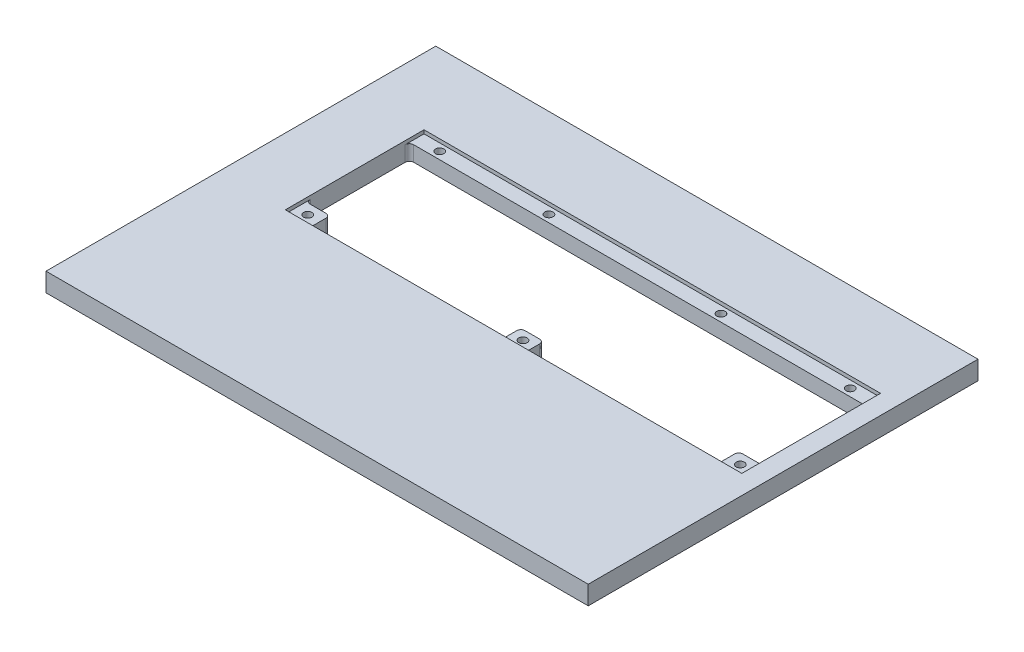
SolidWorks part; units mm, degrees
ref_plane "Front Plane" through (0, 0, 0) normal (0, 0, 1) x (1, 0, 0)
ref_plane "Top Plane" through (0, 0, 0) normal (0, 1, 0) x (1, 0, 0)
ref_plane "Right Plane" through (0, 0, 0) normal (1, 0, 0) x (0, 0, -1)
sketch "Sketch1" plane through (0, 0, 0) normal (0, 1, 0) x (1, 0, 0)
  line L1 (-15, 0) -> (245, 0)
  line L2 (-15, 0) -> (-15, 186.9)
  line L3 (-15, 186.9) -> (245, 186.9)
  line L4 (245, 0) -> (245, 186.9)
  point P5 (0, 0)
  point P6 (0, 0)
  point P7 (0, 0)
  point P8 (0, 0)
  point P9 (0, 0)
  dimension "D1" = 186.9
  dimension "D2" = 260
extrude "Boss-Extrude1" add sketch "Sketch1" along normal blind 9
sketch "Sketch2" plane through (0, 0, 0) normal (0, 1, 0) x (1, 0, 0)
  line L0 (245, 186.9) -> (-15, 186.9) construction
  line L1 (16.91, 149.35) -> (235.81, 149.35)
  line L2 (16.91, 149.35) -> (16.91, 82.85)
  line L3 (16.91, 82.85) -> (235.81, 82.85)
  line L4 (235.81, 149.35) -> (235.81, 82.85)
  dimension "D1" = 37.55
  dimension "D3" = 66.5
  dimension "D4" = 218.9
extrude "Cut-Extrude1" cut sketch "Sketch2" along normal blind 9
sketch "Sketch3" plane through (0, 9, 0) normal (0, 1, 0) x (1, 0, 0)
  line L0 (235.81, 149.35) -> (16.91, 149.35) construction
  line L1 (16.91, 149.35) -> (16.91, 82.85) construction
  line L2 (16.91, 82.85) -> (235.81, 82.85) construction
  circle A0 centre (27.91, 145.85) radius 2
  circle A1 centre (80.31, 145.85) radius 2
  circle A2 centre (162.81, 145.85) radius 2
  circle A3 centre (224.81, 145.85) radius 2
  circle A4 centre (22.66, 87.85) radius 2
  circle A5 centre (126.36, 87.35) radius 2
  circle A6 centre (230.06, 87.85) radius 2
  dimension "D3" = 4
  dimension "D4" = 3.5
  dimension "D6" = 3.5
  dimension "D8" = 3.5
  dimension "D10" = 5
  dimension "D12" = 4.5
  dimension "D14" = 5
  dimension "D1" = 3.5
  dimension "D2" = 11
  dimension "D5" = 52.4
  dimension "D7" = 82.5
  dimension "D9" = 62
  dimension "D11" = 5.75
  dimension "D13" = 103.7
  dimension "D15" = 103.7
sketch "Sketch4" plane through (0, 0, 0) normal (0, 1, 0) x (1, 0, 0)
  line L0 (235.81, 82.85) -> (235.81, 149.35) construction
  line L1 (16.91, 149.35) -> (235.81, 149.35)
  line L2 (16.91, 149.35) -> (16.91, 142.35)
  line L3 (16.91, 142.35) -> (235.81, 142.35)
  line L4 (235.81, 149.35) -> (235.81, 142.35)
  line L5 (16.91, 82.85) -> (235.81, 82.85) construction
  line L6 (235.81, 82.85) -> (224.31, 82.85)
  line L7 (235.81, 82.85) -> (235.81, 92.85)
  line L8 (235.81, 92.85) -> (224.31, 92.85)
  line L9 (224.31, 82.85) -> (224.31, 92.85)
  line L10 (120.86, 82.85) -> (131.86, 82.85)
  line L11 (120.86, 82.85) -> (120.86, 91.85)
  line L12 (120.86, 91.85) -> (131.86, 91.85)
  line L13 (131.86, 82.85) -> (131.86, 91.85)
  line L15 (16.91, 82.85) -> (28.41, 82.85)
  line L16 (16.91, 82.85) -> (16.91, 92.85)
  line L17 (16.91, 92.85) -> (28.41, 92.85)
  line L18 (28.41, 82.85) -> (28.41, 92.85)
  dimension "D1" = 7
  dimension "D2" = 5
  dimension "D3" = 5.75
  dimension "D4" = 4.5
  dimension "D5" = 5.5
  dimension "D6" = 5.5
  dimension "D7" = 5.75
  dimension "D8" = 5
extrude "Boss-Extrude2" add sketch "Sketch4" along normal blind 7.3
extrude "Cut-Extrude2" cut sketch "Sketch3" against normal blind 6.6
fillet "Fillet1" radius 2 12 edges at (16.91, 3.65, -92.85) (28.41, 3.65, -82.85) (28.41, 3.65, -92.85) (16.91, 3.65, -142.35) (235.81, 3.65, -142.35) (235.81, 3.65, -92.85) (224.31, 3.65, -82.85) (224.31, 3.65, -92.85) (120.86, 3.65, -82.85) (131.86, 3.65, -82.85) (131.86, 3.65, -91.85) (120.86, 3.65, -91.85)
